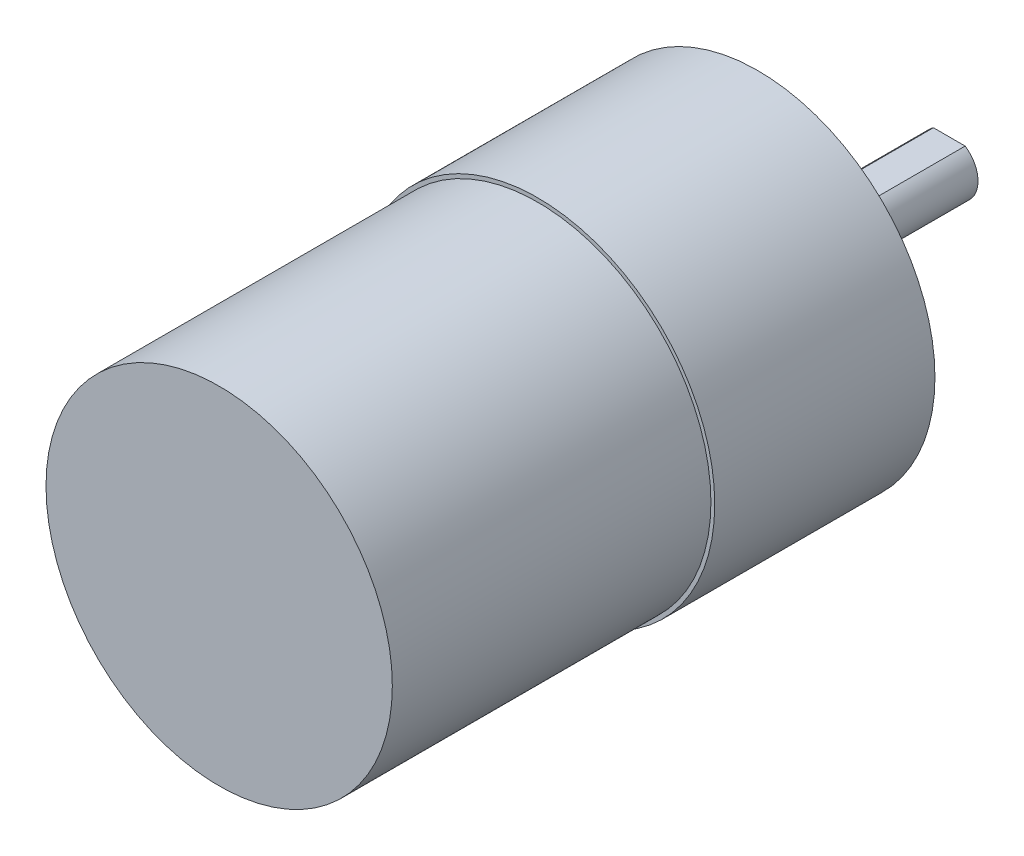
SolidWorks part; units mm, degrees
ref_plane "Front Plane" through (0, 0, 0) normal (0, 0, 1) x (1, 0, 0)
ref_plane "Top Plane" through (0, 0, 0) normal (0, 1, 0) x (1, 0, 0)
ref_plane "Right Plane" through (0, 0, 0) normal (1, 0, 0) x (0, 0, -1)
sketch "Sketch1" plane through (0, 0, 0) normal (0, 0, 1) x (1, 0, 0)
  circle A0 centre (0, 0) radius 18.5
  dimension "D1" = 37
extrude "Boss-Extrude1" add sketch "Sketch1" along normal blind 23.0162
sketch "Sketch2" plane through (0, 0, 23.0162) normal (0, 0, 1) x (1, 0, 0)
  circle A0 centre (0, 0) radius 18.1
  dimension "D1" = 36.2
extrude "Boss-Extrude2" add sketch "Sketch2" along normal blind 33.3
sketch "Sketch3" plane through (0, 0, 0) normal (0, 0, -1) x (-1, 0, 0)
  circle A0 centre (0, 0) radius 6
  dimension "D2" = 12
  dimension "D1" = 0
extrude "Boss-Extrude3" add sketch "Sketch3" along normal blind 5
sketch "Sketch4" plane through (0, 0, -5) normal (0, 0, -1) x (-1, 0, 0)
  arc A0 (-0.5159, 2.9553) -> (0.5159, 2.9553) centre (0, 0) ccw
  arc A1 (-0.5159, 2.9553) -> (0.5159, 2.9553) centre (0, 0) cw
  dimension "D1" = 6
extrude "Boss-Extrude4" add sketch "Sketch4" along normal blind 15
sketch "Sketch5" plane through (0, 0, -20) normal (0, 0, -1) x (-1, 0, 0)
  line L0 (-1.6583, 2.5) -> (1.6583, 2.5)
  line L1 (0, 2.5) -> (0, -3) construction
  circle A0 centre (0, 0) radius 3 construction
  circle A1 centre (0, 0) radius 3 construction
  arc A2 (1.6583, 2.5) -> (-1.6583, 2.5) centre (0, 0) ccw
  dimension "D1" = 5.5
extrude "Cut-Extrude1" cut sketch "Sketch5" against normal blind 14
sketch "Sketch6" plane through (0, 0, 0) normal (0, 0, -1) x (-1, 0, 0)
  line L0 (0, 0) -> (0, 15.5) construction
  line L1 (7.75, 13.4234) -> (0, 0) construction
  circle A0 centre (0, 0) radius 15.5 construction
  circle A2 centre (7.75, 13.4234) radius 1.5
  circle A3 centre (15.5, 0) radius 1.5
  circle A4 centre (7.75, -13.4234) radius 1.5
  circle A5 centre (-7.75, -13.4234) radius 1.5
  circle A6 centre (-15.5, 0) radius 1.5
  circle A7 centre (-7.75, 13.4234) radius 1.5
  point P3 (7.75, 13.4234)
  point P14 (0, 0)
  point P21 (0, 0)
  dimension "D1" = 31
  dimension "D3" = 3
  dimension "D2" = 30
  dimension "D4" = 6
extrude "Cut-Extrude2" cut sketch "Sketch6" against normal blind 8
sketch "Sketch7" plane through (0, 0, 0) normal (0, 0, -1) x (-1, 0, 0)
  circle A1 centre (0, 0) radius 18.5
  circle A2 centre (0, 0) radius 18.5
  circle A4 centre (15.5, 0) radius 1.5 construction
  circle A5 centre (7.75, -13.4234) radius 1.5 construction
  circle A6 centre (-7.75, -13.4234) radius 1.5 construction
  circle A7 centre (-15.5, 0) radius 1.5 construction
  circle A8 centre (-7.75, 13.4234) radius 1.5 construction
  circle A9 centre (7.75, 13.4234) radius 1.5 construction
  circle A10 centre (15.5, 0) radius 1.5
  circle A11 centre (7.75, -13.4234) radius 1.5
  circle A12 centre (-7.75, -13.4234) radius 1.5
  circle A13 centre (-15.5, 0) radius 1.5
  circle A14 centre (-7.75, 13.4234) radius 1.5
  circle A15 centre (7.75, 13.4234) radius 1.5
  circle A16 centre (0, 0) radius 6 construction
  circle A17 centre (0, 0) radius 6
  dimension "D1" = 0
